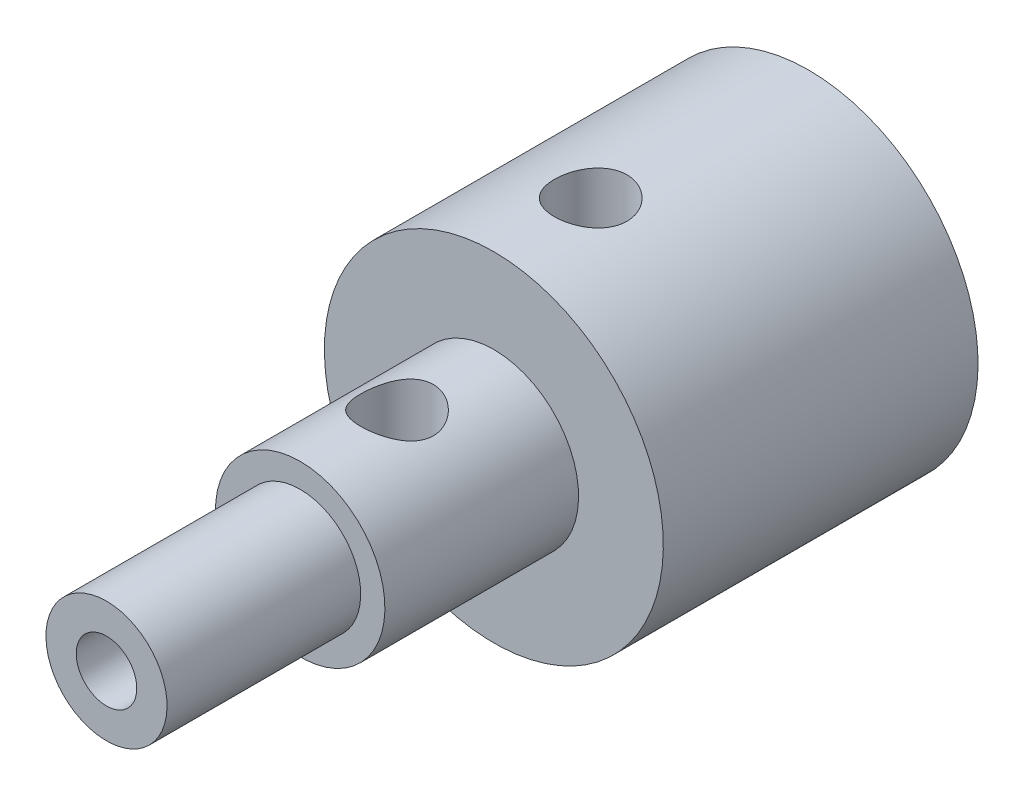
SolidWorks part; units mm, degrees
material "1060 Alloy"
ref_plane "Front Plane" through (0, 0, 0) normal (0, 0, 1) x (1, 0, 0)
ref_plane "Top Plane" through (0, 0, 0) normal (0, 1, 0) x (1, 0, 0)
ref_plane "Right Plane" through (0, 0, 0) normal (1, 0, 0) x (0, 0, -1)
sketch "Sketch1" plane through (0, 0, 0) normal (1, 0, 0) x (0, 0, -1)
  line L0 (0, 0) -> (0, 2.5)
  line L1 (16, 3.5) -> (8, 3.5)
  line L2 (16, 3.5) -> (16, 7)
  line L3 (16.5772, 0) -> (18.5, 3.2)
  line L4 (18.5, 3.2) -> (29, 3.2)
  line L5 (16, 7) -> (29, 7)
  line L6 (29, 3.2) -> (29, 7)
  line L7 (16.5772, 0) -> (0, 0)
  line L8 (8, 3.5) -> (8, 2.5)
  line L9 (8, 2.5) -> (0, 2.5)
  dimension "D1" = 2.5
  dimension "D2" = 8
  dimension "D3" = 3.2
  dimension "D4" = 2.5
  dimension "D5" = 13
  dimension "D6" = 7
  dimension "D7" = 121
  dimension "D8" = 3.5
  dimension "D9" = 8
revolve "Revolve1" add sketch "Sketch1" angle 360 about L7
sketch "Sketch2" plane through (0, 0, 0) normal (0, 1, 0) x (1, 0, 0)
  line L0 (-3.5, 16) -> (3.5, 16) construction
  line L1 (-7, 16) -> (7, 16) construction
  circle A0 centre (0, 20) radius 1.5
  circle A1 centre (0, 12) radius 1.5
  dimension "D2" = 3
  dimension "D3" = 3
  dimension "D1" = 4
  dimension "D4" = 4
extrude "Cut-Extrude1" cut sketch "Sketch2" against normal up to next and the other way up to next
sketch "Sketch4" plane through (0, 0, 0) normal (0, 0, 1) x (1, 0, 0)
  circle A0 centre (0, 0) radius 1.25
  dimension "D1" = 2.5
extrude "Cut-Extrude2" cut sketch "Sketch4" against normal blind 10
